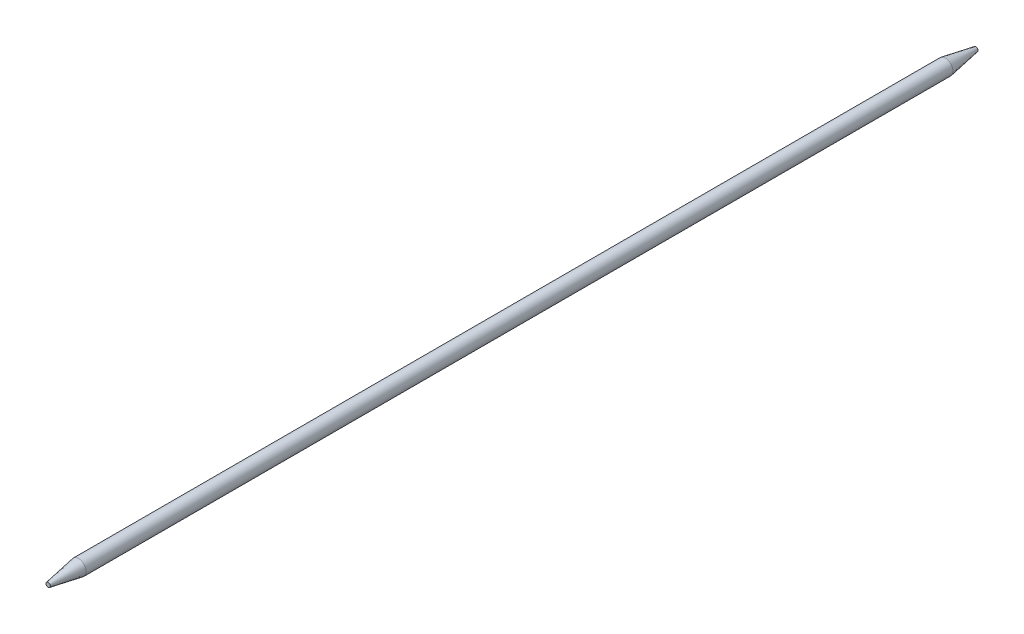
SolidWorks part; units mm, degrees
ref_plane "Front Plane" through (0, 0, 0) normal (0, 0, 1) x (1, 0, 0)
ref_plane "Top Plane" through (0, 0, 0) normal (0, 1, 0) x (1, 0, 0)
ref_plane "Right Plane" through (0, 0, 0) normal (1, 0, 0) x (0, 0, -1)
sketch "Sketch1" plane through (0, 0, 0) normal (0, 0, 1) x (1, 0, 0)
  circle A0 centre (0, 0) radius 88.9
extrude "Boss-Extrude1" add sketch "Sketch1" along normal blind 10972.8
ref_axis "Axis1" through (0, 0, 10972.8) along (0, 0, -1)
ref_plane "Plane1" through (0, 0, 0) normal (1, 0, 0) x (0, 0, -1)
ref_plane "Plane2" through (0, 0, 0) normal (0, -1, 0) x (0, 0, -1)
chamfer "Chamfer1" distance 63.5 angle 80 1 edges at (88.9, 0, 0) first distance on face at (88.9, 0, 0)
chamfer "Chamfer2" distance 63.5 angle 80 1 edges at (88.9, 0, 10972.8) first distance on face at (88.9, 0, 10972.8)
